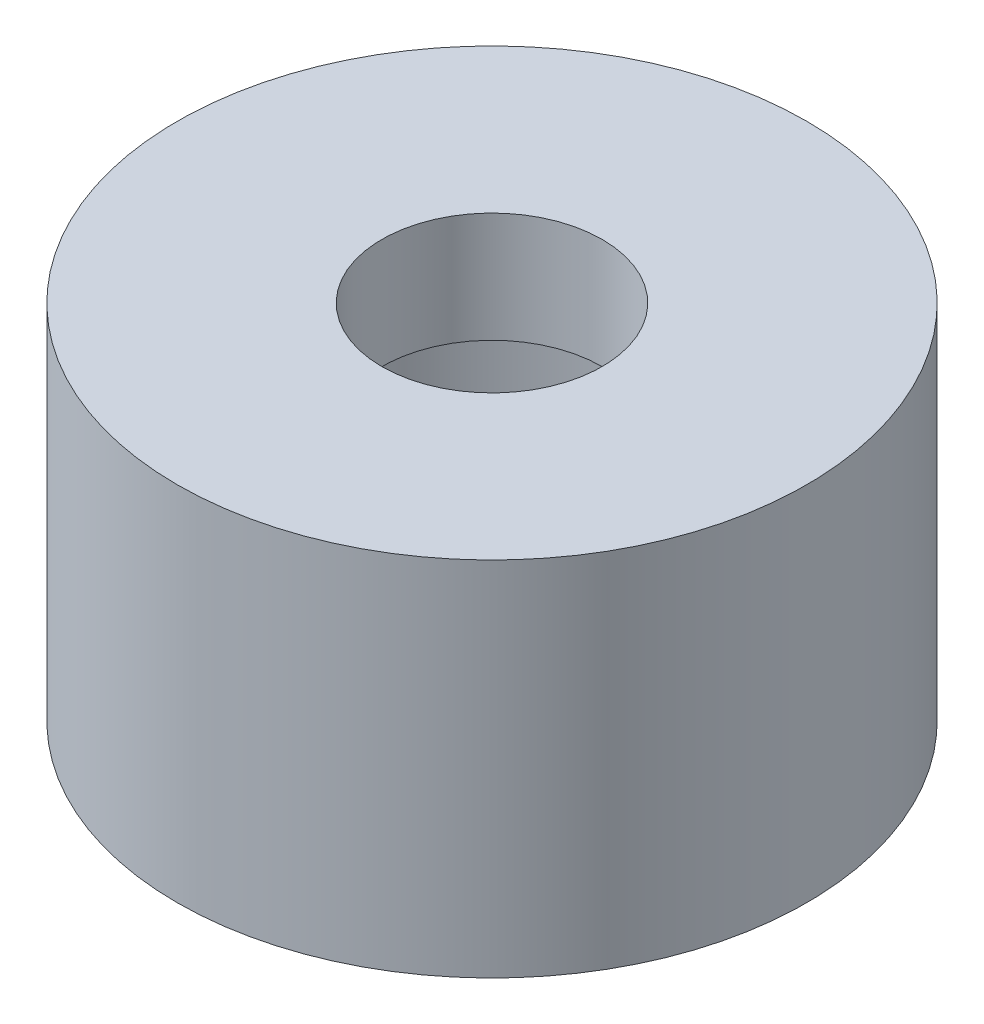
SolidWorks part; units mm, degrees
ref_plane "Front Plane" through (0, 0, 0) normal (0, 0, 1) x (1, 0, 0)
ref_plane "Top Plane" through (0, 0, 0) normal (0, 1, 0) x (1, 0, 0)
ref_plane "Right Plane" through (0, 0, 0) normal (1, 0, 0) x (0, 0, -1)
sketch "Sketch1" plane through (0, 0, 0) normal (0, 1, 0) x (1, 0, 0)
  circle A0 centre (0, 0) radius 7
  circle A1 centre (0, 0) radius 10
  dimension "D1" = 20
  dimension "D2" = 14
extrude "Boss-Extrude1" add sketch "Sketch1" along normal blind 8
sketch "Sketch2" plane through (0, 8, 0) normal (0, 1, 0) x (1, 0, 0)
  circle A0 centre (0, 0) radius 3.5
  circle A1 centre (0, 0) radius 10
  circle A2 centre (0, 0) radius 10
  dimension "D2" = 7
  dimension "D1" = 0
extrude "Boss-Extrude2" add sketch "Sketch2" along normal blind 3.5
